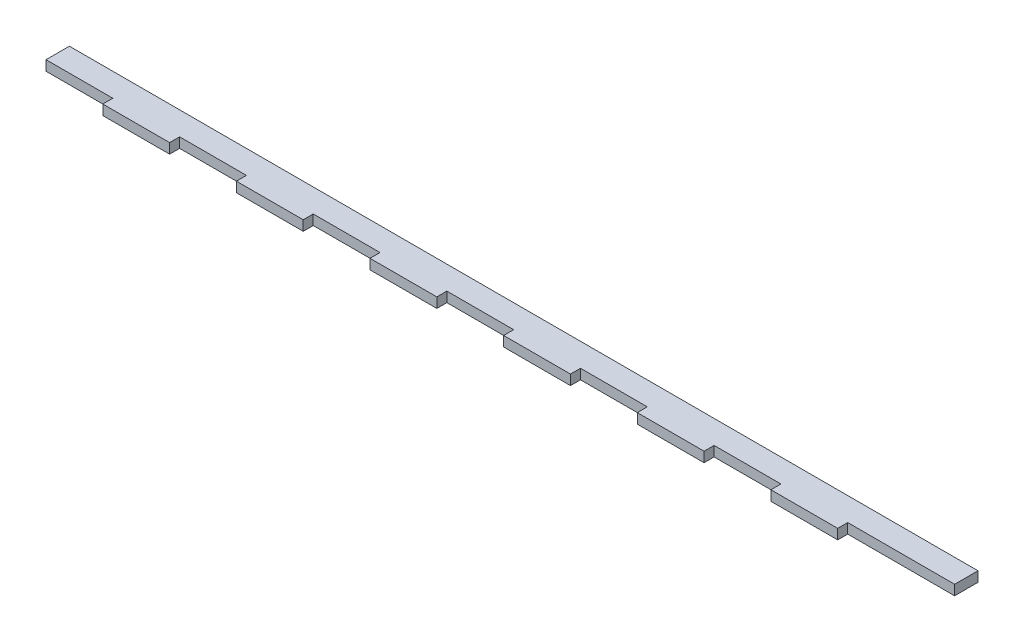
SolidWorks part; units mm, degrees
ref_plane "Alzado" through (0, 0, 0) normal (0, 0, 1) x (1, 0, 0)
ref_plane "Planta" through (0, 0, 0) normal (0, 1, 0) x (1, 0, 0)
ref_plane "Vista lateral" through (0, 0, 0) normal (1, 0, 0) x (0, 0, -1)
sketch "Croquis1" plane through (0, 0, 0) normal (0, 1, 0) x (1, 0, 0)
  line L1 (0, 0) -> (544, 0)
  line L2 (0, 0) -> (0, 20)
  line L3 (0, 20) -> (544, 20)
  line L4 (544, 0) -> (544, 20)
  dimension "D1" = 544
  dimension "D2" = 20
extrude "Saliente-Extruir1" add sketch "Croquis1" along normal blind 6
sketch "Croquis3" plane through (0, 0, 0) normal (0, 1, 0) x (1, 0, 0)
  line L0 (0, 0) -> (544, 0) construction
  line L1 (0, 0) -> (40, 0)
  line L2 (0, 0) -> (0, 6)
  line L3 (0, 6) -> (40, 6)
  line L4 (40, 0) -> (40, 6)
  line L6 (0, 20) -> (0, 0) construction
  point P8 (0, 3)
  dimension "D2" = 40
  dimension "D3" = 6
extrude "Cortar-Extruir1" cut sketch "Croquis3" along normal blind 6
pattern_linear "MatrizL1" count 7 spacing 80 along (1, 0, 0) of "Cortar-Extruir1"
sketch "Croquis4" plane through (0, 6, 0) normal (0, 1, 0) x (1, 0, 0)
  line L1 (520, 6) -> (544, 6)
  line L2 (520, 6) -> (520, 0)
  line L3 (520, 0) -> (544, 0)
  line L4 (544, 6) -> (544, 0)
extrude "Cortar-Extruir2" cut sketch "Croquis4" against normal blind 6
